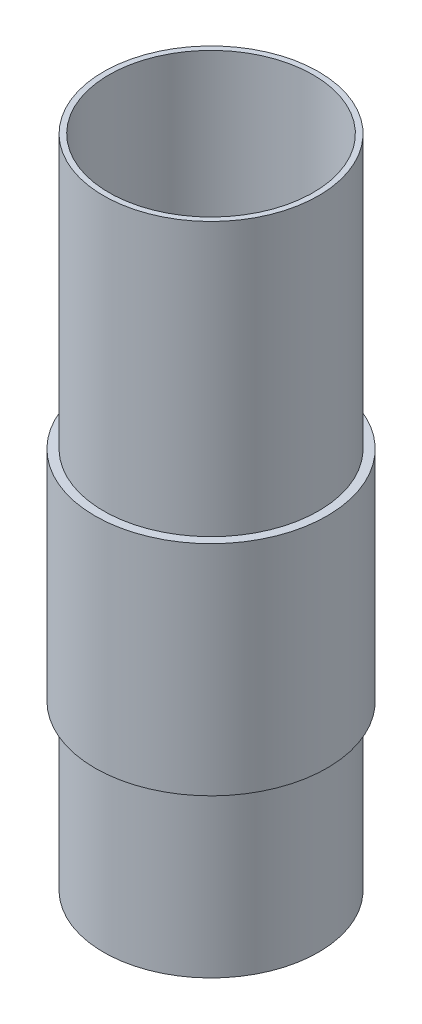
SolidWorks part; units mm, degrees
ref_plane "Front Plane" through (0, 0, 0) normal (0, 0, 1) x (1, 0, 0)
ref_plane "Top Plane" through (0, 0, 0) normal (0, 1, 0) x (1, 0, 0)
ref_plane "Right Plane" through (0, 0, 0) normal (1, 0, 0) x (0, 0, -1)
sketch "Sketch1" plane through (0, 0, 0) normal (0, 1, 0) x (1, 0, 0)
  circle A0 centre (0, 0) radius 23.749
  circle A1 centre (0, 0) radius 25.0063
  dimension "D1" = 47.498
  dimension "D2" = 50.0126
extrude "Boss-Extrude1" add sketch "Sketch1" along normal blind 152.4
ref_plane "Plane1" through (0, 88.9, 0) normal (0, 1, 0) x (1, 0, 0)
sketch "Sketch5" plane through (0, 88.9, 0) normal (0, 1, 0) x (1, 0, 0)
  circle A0 centre (0, 0) radius 25.0063
  circle A1 centre (0, 0) radius 27.0002
  dimension "D1" = 54.0004
  dimension "D2" = 50.0126
extrude "Boss-Extrude3" add sketch "Sketch5" against normal blind 50.8
